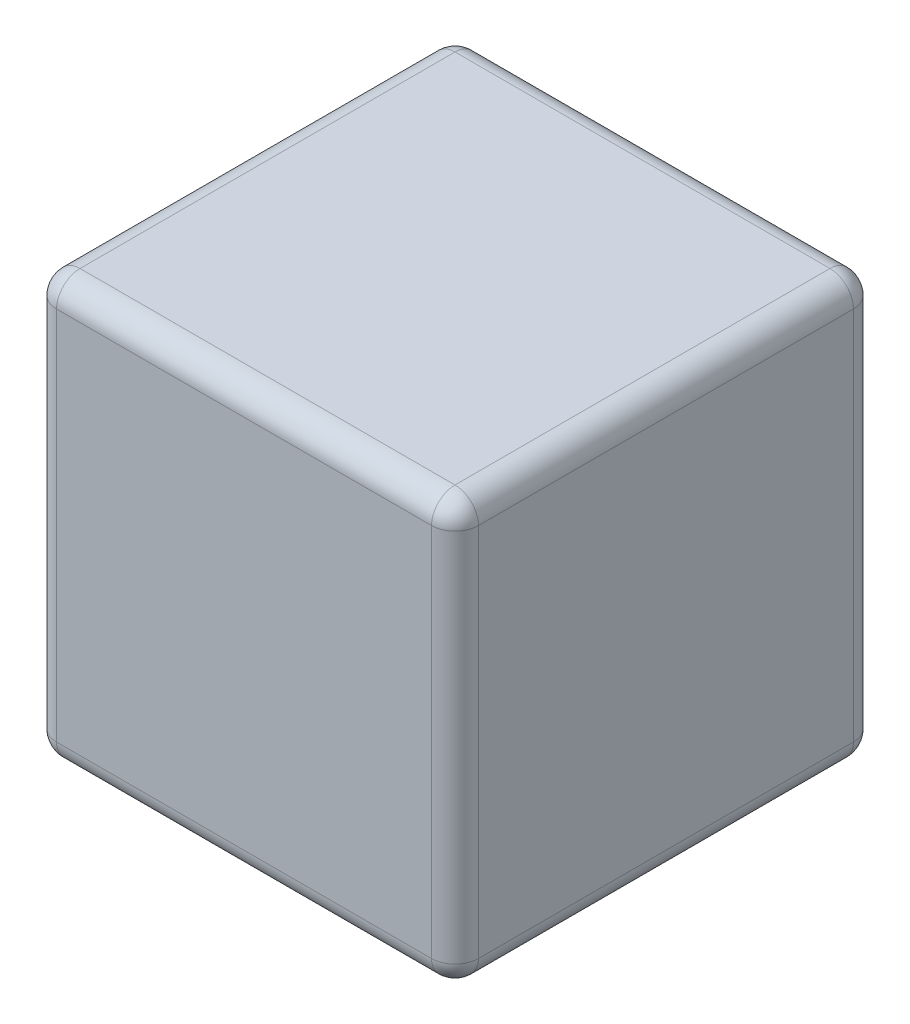
SolidWorks part; units mm, degrees
ref_plane "Front Plane" through (0, 0, 0) normal (0, 0, 1) x (1, 0, 0)
ref_plane "Top Plane" through (0, 0, 0) normal (0, 1, 0) x (1, 0, 0)
ref_plane "Right Plane" through (0, 0, 0) normal (1, 0, 0) x (0, 0, -1)
sketch "Sketch1" plane through (0, 0, 0) normal (0, 0, 1) x (1, 0, 0)
  line L1 (0, 0) -> (10, 0)
  line L2 (0, 0) -> (0, 10)
  line L3 (0, 10) -> (5, 10)
  line L4 (10, 0) -> (10, 5)
  arc A0 (10, 5) -> (5, 10) centre (-0.6086, -0.6086) ccw
  dimension "D1" = 10
  dimension "D2" = 10
extrude "Boss-Extrude1" add sketch "Sketch1" along normal blind 10
sketch "Sketch2" plane through (0, 0, 0) normal (0, 1, 0) x (1, 0, 0)
  line L2 (0, 0) -> (10, 0)
  line L3 (0, 0) -> (0, -10)
  line L4 (0, -10) -> (10, -10)
  line L5 (10, 0) -> (10, -10)
  arc A0 (5, -10) -> (10, -5) centre (-0.6086, 0.6086) ccw
extrude "Cut-Extrude1" cut sketch "Sketch2" against normal blind 10 and the other way blind 10 flip side to cut contours L4 A0 L5 L2 L3 region at (4.6114, 0, 4.6114)
sketch "Sketch3" plane through (0, 0, 0) normal (1, 0, 0) x (0, 0, -1)
  line L1 (0, 0) -> (-10, 0)
  line L2 (0, 0) -> (0, 10)
  line L3 (0, 10) -> (-10, 10)
  line L4 (-10, 0) -> (-10, 10)
  arc A0 (-10, 5) -> (-5, 10) centre (0.6086, -0.6086) cw
extrude "Cut-Extrude4" cut sketch "Sketch3" against normal blind 10 and the other way blind 10 flip side to cut contours A0 L4 L1 L2 L3 region at (0, 4.6114, 4.6114)
sketch "Sketch4" plane through (0, 0, 0) normal (0, 0, 1) x (1, 0, 0)
  line L1 (5, 5) -> (23, 5)
  line L2 (5, 5) -> (5, 23)
  line L3 (5, 23) -> (23, 23)
  line L4 (23, 5) -> (23, 23)
  dimension "D1" = 5
  dimension "D2" = 5
  dimension "D3" = 18
  dimension "D4" = 18
extrude "Boss-Extrude2" add sketch "Sketch4" along normal blind 23
sketch "Sketch5" plane through (0, 0, 0) normal (0, 0, 1) x (1, 0, 0)
  line L1 (23, 23) -> (5, 23)
  line L2 (23, 23) -> (23, 5)
  line L3 (23, 5) -> (5, 5)
  line L4 (5, 23) -> (5, 5)
  arc A0 (5, 10) -> (10, 5) centre (-0.6086, -0.6086) cw
  dimension "D1" = 18
  dimension "D2" = 18
extrude "Cut-Extrude6" cut sketch "Sketch5" against normal blind 5 and the other way blind 5 contours L4 A0 L3 L2 L1 region at (14.3485, 14.3485, 0)
fillet "Fillet1" radius 1 12 edges at (23, 14, 5) (23, 5, 14) (23, 14, 23) (14, 5, 23) (5, 14, 23) (14, 23, 23) (5, 23, 14) (14, 23, 5) (23, 23, 14) (5, 16.5, 5) (5, 5, 16.5) (16.5, 5, 5)
fillet "Fillet4" radius 0.4 18 edges at (10, 2.5, 5) (10, 5, 2.5) (5, 10, 2.5) (2.5, 10, 5) (2.5, 5, 10) (5, 2.5, 10) (0, 2.5, 10) (0, 10, 2.5) (0, 7.8766, 7.8766) (2.5, 10, 0) (0, 5, 0) (10, 2.5, 0) (7.8766, 7.8766, 0) (5, 0, 0) (0, 0, 5) (2.5, 0, 10) (7.8766, 0, 7.8766) (10, 0, 2.5)
fillet "Fillet5" radius 0.4 9 edges at (5.5851, 9.6694, 5.0901) (9.6743, 5.5769, 5.0939) (7.8766, 7.8766, 5) (5.5769, 5.0939, 9.6743) (9.6694, 5.0901, 5.5851) (7.8766, 5, 7.8766) (5.0901, 5.5851, 9.6694) (5.0939, 9.6743, 5.5769) (5, 7.8766, 7.8766)
